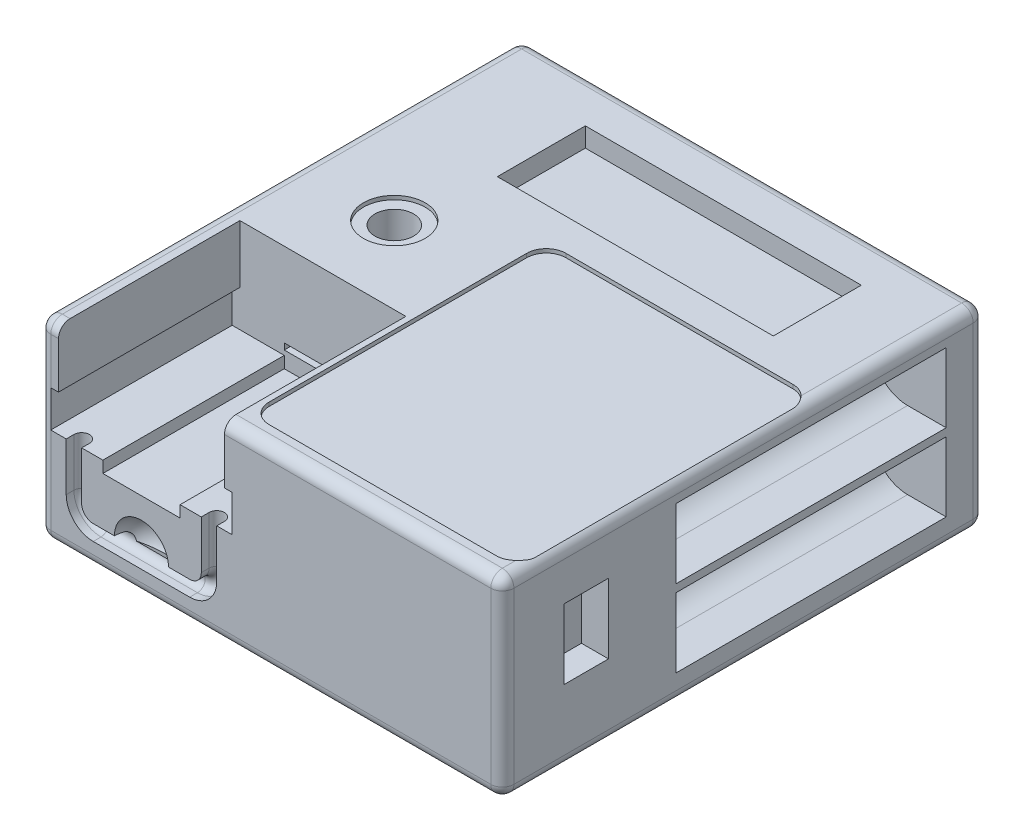
SolidWorks part; units mm, degrees
ref_plane "Front Plane" through (0, 0, 0) normal (0, 0, 1) x (1, 0, 0)
ref_plane "Top Plane" through (0, 0, 0) normal (0, 1, 0) x (1, 0, 0)
ref_plane "Right Plane" through (0, 0, 0) normal (1, 0, 0) x (0, 0, -1)
sketch "Sketch1" plane through (0, 0, 0) normal (0, 1, 0) x (1, 0, 0)
  line L1 (0, 0) -> (120, 0)
  line L2 (0, 0) -> (0, 125)
  line L3 (0, 125) -> (120, 125)
  line L4 (120, 0) -> (120, 125)
  dimension "D1" = 120
  dimension "D2" = 125
extrude "Boss-Extrude1" add sketch "Sketch1" along normal blind 70
sketch "Sketch3" plane through (0, 0, 0) normal (0, 0, 1) x (1, 0, 0)
  line L0 (0, 70) -> (120, 70) construction
  line L1 (3, 55) -> (50, 55)
  line L2 (3, 55) -> (3, 45.5)
  line L3 (3, 45.5) -> (50, 45.5)
  line L4 (50, 55) -> (50, 45.5)
  line L5 (0, 70) -> (0, 0) construction
  dimension "D1" = 47
  dimension "D2" = 9.5
  dimension "D3" = 15
  dimension "D4" = 3
extrude "Cut-Extrude1" cut sketch "Sketch3" against normal blind 47
sketch "Sketch4" plane through (0, 0, 0) normal (0, 0, 1) x (1, 0, 0)
  line L0 (0, 70) -> (120, 70) construction
  line L1 (5, 70) -> (48, 70)
  line L2 (5, 70) -> (5, 55)
  line L3 (5, 55) -> (48, 55)
  line L4 (48, 70) -> (48, 55)
  line L5 (50, 55) -> (3, 55) construction
  line L6 (3, 55) -> (3, 45.5) construction
  line L7 (50, 45.5) -> (50, 55) construction
  dimension "D1" = 2
  dimension "D2" = 2
extrude "Cut-Extrude2" cut sketch "Sketch4" against normal blind 47
sketch "Sketch5" plane through (0, 0, 0) normal (0, 0, 1) x (1, 0, 0)
  line L0 (9, 45.5) -> (9, 33)
  line L1 (3, 45.5) -> (50, 45.5) construction
  line L2 (14, 28) -> (39, 28)
  line L3 (44, 33) -> (44, 45.5)
  line L4 (3, 45.5) -> (50, 45.5) construction
  line L5 (3, 55) -> (3, 45.5) construction
  line L6 (50, 45.5) -> (50, 55) construction
  arc A0 (39, 28) -> (44, 33) centre (39, 33) ccw
  arc A1 (9, 33) -> (14, 28) centre (14, 33) ccw
  point P14 (44, 28)
  dimension "D4" = 5
  dimension "D1" = 6
  dimension "D2" = 17.5
  dimension "D3" = 6
sketch "Sketch6" plane through (0, 45.5, 0) normal (0, 1, 0) x (1, 0, 0)
  line L0 (7, 0) -> (7, 2)
  line L1 (3, 0) -> (50, 0) construction
  line L2 (11, 2) -> (11, 0)
  line L3 (11, 0) -> (7, 0)
  arc A0 (7, 2) -> (11, 2) centre (9, 2) cw
  dimension "D1" = 2
  dimension "D2" = 2
sweep "Cut-Sweep1" cut profiles "Sketch6" path "Sketch5"
sketch "Sketch7" plane through (0, 0, 0) normal (0, 0, 1) x (1, 0, 0)
  line L0 (14, 30) -> (39, 30) construction
  line L1 (14, 30) -> (39, 30) construction
  line L2 (19.5, 30) -> (33.5, 30)
  arc A0 (19.5, 30) -> (33.5, 30) centre (26.5, 30) cw
  dimension "D1" = 7
revolve "Cut-Revolve1" cut sketch "Sketch7" angle 120 about L2 reverse direction yes
sketch "Sketch9" plane through (0, 45.5, 0) normal (0, 1, 0) x (1, 0, 0)
  line L0 (48, 47) -> (5, 47) construction
  line L1 (16.5, 47) -> (36.5, 47)
  line L2 (16.5, 47) -> (16.5, 0)
  line L3 (16.5, 0) -> (36.5, 0)
  line L4 (36.5, 47) -> (36.5, 0)
  line L5 (11, 0) -> (42, 0) construction
  line L7 (3, 47) -> (3, 0) construction
  dimension "D1" = 20
  dimension "D2" = 13.5
extrude "Cut-Extrude3" cut sketch "Sketch9" against normal blind 3
sketch "Sketch10" plane through (0, 0, -47) normal (0, 0, 1) x (1, 0, 0)
  line L0 (3, 45.5) -> (16.5, 45.5) construction
  line L1 (16.5, 48.3) -> (36.5, 48.3)
  line L2 (16.5, 48.3) -> (16.5, 46.7)
  line L3 (16.5, 46.7) -> (36.5, 46.7)
  line L4 (36.5, 48.3) -> (36.5, 46.7)
  line L5 (3, 55) -> (3, 45.5) construction
  dimension "D1" = 1.2
  dimension "D2" = 20
  dimension "D3" = 13.5
  dimension "D4" = 1.6
extrude "Cut-Extrude4" cut sketch "Sketch10" against normal blind 3.5
sketch "Sketch11" plane through (0, 70, 0) normal (0, 1, 0) x (1, 0, 0)
  line L0 (48, 47) -> (48, 0) construction
  line L1 (54.58, 81.89) -> (113.38, 81.89)
  line L2 (49.5, 76.81) -> (49.5, 10.08)
  line L3 (54.58, 5) -> (113.38, 5)
  line L4 (118.46, 76.81) -> (118.46, 10.08)
  line L5 (48, 0) -> (120, 0) construction
  arc A0 (49.5, 10.08) -> (54.58, 5) centre (54.58, 10.08) ccw
  arc A1 (113.38, 5) -> (118.46, 10.08) centre (113.38, 10.08) ccw
  arc A2 (113.38, 81.89) -> (118.46, 76.81) centre (113.38, 76.81) cw
  arc A3 (54.58, 81.89) -> (49.5, 76.81) centre (54.58, 76.81) ccw
  point P12 (118.46, 5)
  point P15 (118.46, 81.89)
  point P18 (49.5, 81.89)
  dimension "D5" = 5.08
  dimension "D1" = 68.96
  dimension "D2" = 76.89
  dimension "D3" = 1.5
  dimension "D4" = 5
extrude "Cut-Extrude5" cut sketch "Sketch11" against normal blind 1
sketch "Sketch13" plane through (0, 70, 0) normal (0, 1, 0) x (1, 0, 0)
  line L0 (120, 125) -> (0, 125) construction
  line L1 (28.5, 113) -> (100, 113)
  line L2 (28.5, 113) -> (28.5, 90.2)
  line L3 (28.5, 90.2) -> (100, 90.2)
  line L4 (100, 113) -> (100, 90.2)
  line L5 (120, 0) -> (120, 125) construction
  dimension "D1" = 71.5
  dimension "D2" = 22.8
  dimension "D3" = 12
  dimension "D4" = 20
extrude "Cut-Extrude6" cut sketch "Sketch13" against normal blind 5
sketch "Sketch14" plane through (0, 70, 0) normal (0, 1, 0) x (1, 0, 0)
  line L0 (120, 125) -> (0, 125) construction
  line L1 (0, 125) -> (0, 0) construction
  circle A0 centre (25, 67) radius 5
  dimension "D1" = 10
  dimension "D2" = 58
  dimension "D3" = 25
extrude "Cut-Extrude7" cut sketch "Sketch14" against normal blind 10
sketch "Sketch15" plane through (0, 70, 0) normal (0, 1, 0) x (1, 0, 0)
  circle A0 centre (25, 67) radius 8
  dimension "D1" = 16
extrude "Cut-Extrude8" cut sketch "Sketch15" against normal blind 1
sketch "Sketch16" plane through (120, 0, 0) normal (1, 0, 0) x (0, 0, -1)
  line L0 (0, 70) -> (125, 70) construction
  line L1 (45, 65) -> (115, 65)
  line L2 (45, 65) -> (45, 47)
  line L3 (45, 47) -> (115, 47)
  line L4 (115, 65) -> (115, 47)
  line L5 (125, 70) -> (125, 0) construction
  line L7 (45, 45) -> (115, 45)
  line L8 (45, 45) -> (45, 27)
  line L9 (45, 27) -> (115, 27)
  line L10 (115, 45) -> (115, 27)
  dimension "D1" = 18
  dimension "D2" = 70
  dimension "D3" = 5
  dimension "D4" = 10
  dimension "D5" = 18
  dimension "D6" = 70
  dimension "D7" = 2
  dimension "D8" = 10
extrude "Cut-Extrude9" cut sketch "Sketch16" against normal blind 10
sketch "Sketch17" plane through (110, 0, 0) normal (1, 0, 0) x (0, 0, -1)
  line L4 (45, 56) -> (115, 56) construction
  line L5 (45, 56) -> (115, 56)
  line L8 (45, 65) -> (45, 47)
  line L9 (45, 47) -> (115, 47)
  line L10 (115, 47) -> (115, 65)
  line L11 (115, 65) -> (45, 65)
  line L12 (45, 65) -> (45, 56)
  line L14 (115, 56) -> (115, 65)
  line L15 (115, 65) -> (45, 65)
  dimension "D1" = 0
revolve "Cut-Revolve2" cut sketch "Sketch17" angle 360 about L4
sketch "Sketch18" plane through (110, 0, 0) normal (1, 0, 0) x (0, 0, -1)
  line L4 (45, 36) -> (115, 36)
  line L8 (45, 45) -> (45, 27)
  line L9 (45, 27) -> (115, 27)
  line L10 (115, 27) -> (115, 45)
  line L11 (115, 45) -> (45, 45)
  line L12 (45, 45) -> (45, 36)
  line L14 (115, 36) -> (115, 45)
  line L15 (115, 45) -> (45, 45)
  dimension "D1" = 0
revolve "Cut-Revolve3" cut sketch "Sketch18" angle 360 about L4
sketch "Sketch19" plane through (0, 0, 0) normal (-1, 0, 0) x (0, 0, 1)
  line L0 (-125, 70) -> (0, 70) construction
  line L1 (-115, 45) -> (-55, 45)
  line L2 (-115, 45) -> (-115, 30)
  line L3 (-115, 30) -> (-55, 30)
  line L4 (-55, 45) -> (-55, 30)
  line L5 (-125, 70) -> (-125, 0) construction
  dimension "D1" = 60
  dimension "D2" = 15
  dimension "D3" = 25
  dimension "D4" = 10
extrude "Cut-Extrude10" cut sketch "Sketch19" against normal blind 60
sketch "Sketch20" plane through (0, 0, 0) normal (-1, 0, 0) x (0, 0, 1)
  line L0 (-55, 45) -> (-115, 45) construction
  line L1 (-55, 45) -> (-115, 45) construction
  line L2 (-95, 45) -> (-75, 45)
  arc A0 (-95, 45) -> (-75, 45) centre (-85, 45) cw
  dimension "D1" = 10
revolve "Cut-Revolve4" cut sketch "Sketch20" angle 90 about L2 reverse direction yes
sketch "Sketch21" plane through (0, 0, 0) normal (0, -1, 0) x (1, 0, 0)
  line L8 (0, 0) -> (0, -125)
  line L9 (0, -125) -> (120, -125)
  line L10 (120, -125) -> (120, 0)
  line L11 (120, 0) -> (0, 0)
  line L12 (0, 0) -> (0, -125)
  line L13 (0, -125) -> (120, -125)
  line L14 (120, -125) -> (120, 0)
  line L15 (120, 0) -> (0, 0)
  dimension "D1" = 0
extrude "Cut-Extrude11" cut sketch "Sketch21" against normal blind 20
fillet "Fillet1" radius 3 8 edges at (120, 20, -62.5) (60, 20, 0) (0, 20, -62.5) (60, 20, -125) (0, 45, -125) (120, 45, -125) (120, 45, 0) (0, 45, 0)
fillet "Fillet2" radius 3 9 edges at (82.5, 70, 0) (119.1213, 70, -0.8787) (120, 70, -62.5) (119.1213, 70, -124.1213) (60, 70, -125) (0.8787, 70, -124.1213) (4, 70, 0) (0.8787, 70, -0.8787) (0, 70, -62.5)
sketch "Sketch22" plane through (120, 0, 0) normal (1, 0, 0) x (0, 0, -1)
  line L0 (122, 67) -> (3, 67) construction
  line L1 (16, 57) -> (27.5, 57)
  line L2 (16, 57) -> (16, 38.9)
  line L3 (16, 38.9) -> (27.5, 38.9)
  line L4 (27.5, 57) -> (27.5, 38.9)
  line L5 (3, 67) -> (3, 23) construction
  dimension "D1" = 11.5
  dimension "D2" = 18.1
  dimension "D3" = 10
  dimension "D4" = 13
extrude "Cut-Extrude12" cut sketch "Sketch22" against normal blind 7
